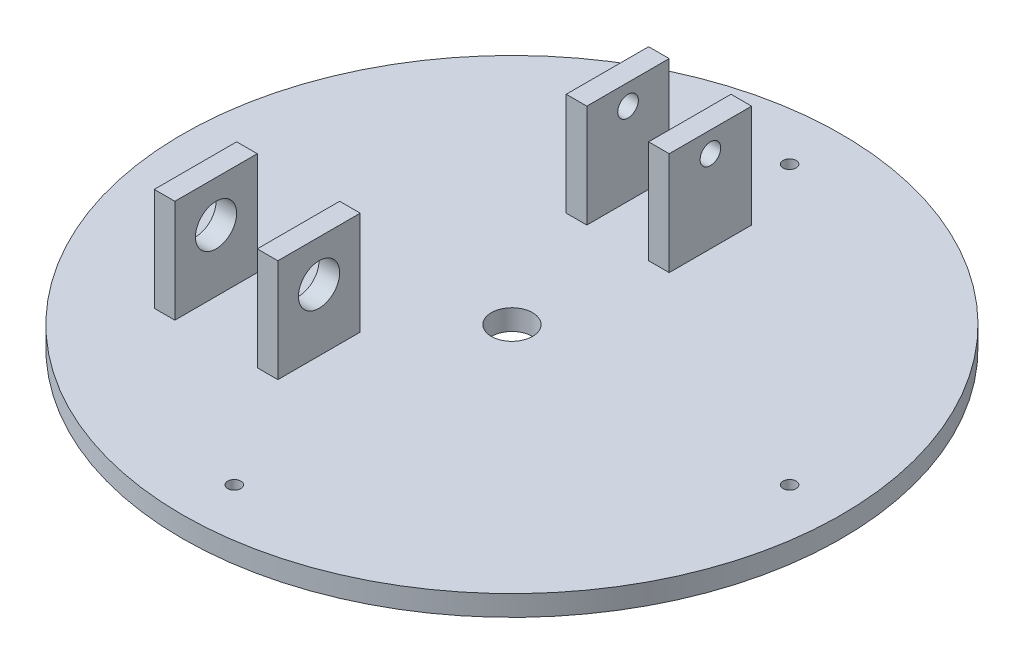
SolidWorks part; units mm, degrees
material "6061 Alloy"
ref_plane "Front Plane" through (0, 0, 0) normal (0, 0, 1) x (1, 0, 0)
ref_plane "Top Plane" through (0, 0, 0) normal (0, 1, 0) x (1, 0, 0)
ref_plane "Right Plane" through (0, 0, 0) normal (1, 0, 0) x (0, 0, -1)
sketch "Sketch1" plane through (0, 0, 0) normal (0, 1, 0) x (1, 0, 0)
  circle A0 centre (0, 0) radius 101.6
  dimension "D1" = 203.2
extrude "Boss-Extrude1" add sketch "Sketch1" along normal blind 6.35
sketch "Sketch2" plane through (0, 0, 0) normal (0, -1, 0) x (1, 0, 0)
  circle A0 centre (0, 0) radius 6.35
  dimension "D1" = 12.7
extrude "Cut-Extrude1" cut sketch "Sketch2" against normal through all
sketch "Sketch3" plane through (0, 6.35, 0) normal (0, 1, 0) x (1, 0, 0)
  line L0 (-53.1127, -38.1) -> (-27.7127, -38.1) construction
  line L1 (-59.4627, -25.4) -> (-53.1127, -25.4)
  line L2 (-59.4627, -25.4) -> (-59.4627, -50.8)
  line L3 (-59.4627, -50.8) -> (-53.1127, -50.8)
  line L4 (-53.1127, -25.4) -> (-53.1127, -50.8)
  line L5 (-27.7127, -25.4) -> (-21.3627, -25.4)
  line L6 (-27.7127, -25.4) -> (-27.7127, -50.8)
  line L7 (-27.7127, -50.8) -> (-21.3627, -50.8)
  line L8 (-21.3627, -25.4) -> (-21.3627, -50.8)
  point P10 (-40.4127, -38.1)
  dimension "D1" = 40.4127
  dimension "D2" = 6.35
  dimension "D3" = 38.1
  dimension "D4" = 25.4
  dimension "D5" = 25.4
extrude "Boss-Extrude2" add sketch "Sketch3" along normal blind 31.75
sketch "Sketch4" plane through (-21.3627, 0, 0) normal (1, 0, 0) x (0, 0, -1)
  line L0 (-38.1, 38.1) -> (-38.1, 25.4) construction
  line L1 (-50.8, 38.1) -> (-25.4, 38.1) construction
  circle A0 centre (-38.1, 25.4) radius 6.35
  dimension "D1" = 12.7
  dimension "D2" = 12.7
extrude "Cut-Extrude2" cut sketch "Sketch4" against normal up to surface (38.1 mm away) up to face at (-59.4627, 22.225, 38.1)
sketch "Sketch5" plane through (0, 6.35, 0) normal (0, 1, 0) x (1, 0, 0)
  line L0 (-15.0127, 50.8) -> (4.0373, 50.8) construction
  line L2 (-21.3627, 38.1) -> (-15.0127, 38.1)
  line L3 (-21.3627, 38.1) -> (-21.3627, 63.5)
  line L4 (-21.3627, 63.5) -> (-15.0127, 63.5)
  line L5 (-15.0127, 38.1) -> (-15.0127, 63.5)
  line L6 (4.0373, 63.5) -> (10.3873, 63.5)
  line L7 (4.0373, 63.5) -> (4.0373, 38.1)
  line L8 (4.0373, 38.1) -> (10.3873, 38.1)
  line L9 (10.3873, 63.5) -> (10.3873, 38.1)
  point P10 (-5.4877, 50.8)
  dimension "D1" = 25.4
  dimension "D2" = 6.35
  dimension "D3" = 19.05
  dimension "D4" = 34.925
  dimension "D5" = 88.9
extrude "Boss-Extrude3" add sketch "Sketch5" along normal blind 31.75
sketch "Sketch6" plane through (-21.3627, 0, 0) normal (-1, 0, 0) x (0, 0, 1)
  line L0 (-50.8, 38.1) -> (-50.8, 31.75) construction
  line L1 (-63.5, 38.1) -> (-38.1, 38.1) construction
  circle A0 centre (-50.8, 31.75) radius 3.175
  dimension "D1" = 6.35
  dimension "D2" = 6.35
extrude "Cut-Extrude3" cut sketch "Sketch6" against normal up to surface (31.75 mm away) up to face at (10.3873, 22.225, -50.8)
hole_wizard "#10-32 Tapped Hole1" positions "Sketch8" profile "Sketch7" tap size "#10-32" standard "ANSI Inch"
sketch "Sketch8" plane through (0, 0, 0) normal (0, -1, 0) x (-1, 0, 0)
  line L1 (85.5998, 0) -> (0, 85.5998)
  line L2 (85.5998, 0) -> (0, -85.5998)
  line L3 (0, 85.5998) -> (-85.5998, 0)
  line L4 (0, -85.5998) -> (-85.5998, 0)
  line L5 (85.5998, 0) -> (-85.5998, 0) construction
  line L6 (0, 85.5998) -> (0, -85.5998) construction
  point P252 (0, 0)
  point P331 (0, -85.5998)
  point P333 (-85.5998, 0)
  point P335 (0, 85.5998)
  point P337 (85.5998, 0)
  dimension "D1" = 121.0564
sketch "Sketch7" plane through (0, 0, 0) normal (1, 0, 0) x (0, 0, -1)
  line L0 (0, 0) -> (0, 13.2428)
  line L1 (0, 13.2428) -> (2.0193, 12.0294)
  line L2 (2.0193, 12.0294) -> (2.0193, 0)
  line L5 (2.0193, 0) -> (0, 0)
  line L10 (0, 13.2428) -> (-2.0193, 12.0294) construction
  line L11 (0, -6.35) -> (0, 107.95) construction
  dimension "Tap Drill Dia." = 4.0386
  dimension "Tap Drill Depth" = 12.0294
  dimension "Drill Angle" = 118
